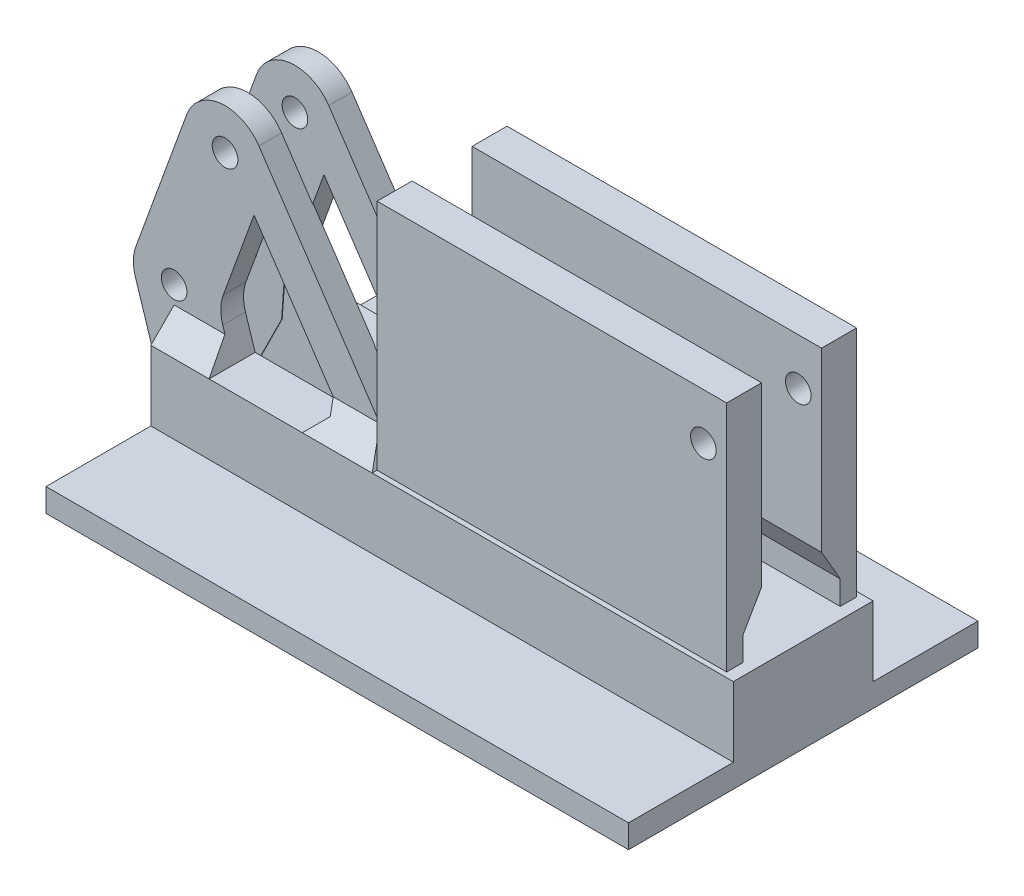
SolidWorks part; units mm, degrees
material "ABS"
ref_plane "前视基准面" through (0, 0, 0) normal (0, 0, 1) x (1, 0, 0)
ref_plane "上视基准面" through (0, 0, 0) normal (0, 1, 0) x (1, 0, 0)
ref_plane "右视基准面" through (0, 0, 0) normal (1, 0, 0) x (0, 0, -1)
other "Configuration Table"
sketch "草图1" plane through (0, 0, 0) normal (0, 1, 0) x (1, 0, 0)
  line L1 (-25, 15) -> (25, 15)
  line L2 (-25, 15) -> (-25, -15)
  line L3 (-25, -15) -> (25, -15)
  line L4 (25, 15) -> (25, -15)
  line L5 (-25, 15) -> (25, -15) construction
  line L6 (-25, -15) -> (25, 15) construction
  point P0 (0, 0)
  dimension "D1" = 30
  dimension "D2" = 50
extrude "凸台-拉伸1" add sketch "草图1" along normal mid plane 8
sketch "草图2" plane through (0, 0, 0) normal (0, 0, 1) x (1, 0, 0)
  line L0 (-25, 7.5) -> (-20.6324, 19.5) construction
  line L1 (-25, 4) -> (25, 4) construction
  line L2 (-25, 4) -> (-25, -4) construction
  line L3 (-25, -4) -> (-28.334, 6.4348)
  line L4 (-28.2889, 8.6971) -> (-23.9213, 20.6971)
  line L5 (-17.3434, 18.3029) -> (-20.7828, 8.8533)
  line L6 (-20.8278, 6.591) -> (-20, 4)
  line L7 (-25, -4) -> (-20, 4)
  circle A0 centre (-25, 7.5) radius 1.1
  circle A1 centre (-20.6324, 19.5) radius 1.1
  arc A2 (-28.334, 6.4348) -> (-28.2889, 8.6971) centre (-25, 7.5) cw
  arc A3 (-23.9213, 20.6971) -> (-17.3434, 18.3029) centre (-20.6324, 19.5) cw
  arc A4 (-20.7828, 8.8533) -> (-20.8278, 6.591) centre (-17.4939, 7.6563) ccw
  dimension "D4" = 2.2
  dimension "D5" = 3.5
  dimension "D1" = 15.5
  dimension "D2" = 70
  dimension "D3" = 3.5
  dimension "D6" = 5
extrude "凸台-拉伸2" add sketch "草图2" along normal mid plane 8
sketch "草图3" plane through (0, 0, 0) normal (0, 0, 1) x (1, 0, 0)
  line L0 (-28.1087, 9.1922) -> (-25.3291, 16.8291)
  line L2 (-23.9213, 20.6971) -> (-28.2889, 8.6971) construction
  line L3 (-20.7828, 8.8533) -> (-18.7512, 14.435)
  line L5 (-20.7828, 8.8533) -> (-17.3434, 18.3029) construction
  line L6 (-25, 7.5) -> (-20.6324, 19.5) construction
  line L7 (-28.2889, 8.6971) -> (-23.9213, 20.6971)
  line L8 (-21.7111, 6.3029) -> (-17.3434, 18.3029)
  line L9 (-25, -4) -> (-28.334, 6.4348)
  line L10 (-25, -4) -> (-21.7111, 6.3029)
  line L11 (-28.334, 6.4348) -> (-25, -4) construction
  line L12 (-21.7111, 6.3029) -> (-20.5376, 5.9283)
  line L13 (-20.5376, 5.9283) -> (-20.7828, 8.8533)
  arc A3 (-28.2889, 8.6971) -> (-21.7111, 6.3029) centre (-25, 7.5) ccw
  arc A4 (-17.3434, 18.3029) -> (-23.9213, 20.6971) centre (-20.6324, 19.5) ccw
  arc A5 (-20.7828, 8.8533) -> (-20.8278, 6.591) centre (-17.4939, 7.6563) ccw construction
  point P3 (-22.8162, 13.5)
extrude "切除-拉伸1" cut sketch "草图3" against normal mid plane 4 contours L8 A4 L7 L0 A3 L3 | A3 L9 L10 | L12 L13 L8 region at (-22.8162, 13.5, 0) region at (-25.0015, 1.6723, 0) region at (-21.0105, 7.0282, 0)
sketch "草图4" plane through (0, 0, 4) normal (0, 0, 1) x (1, 0, 0)
  line L0 (-17.7273, 21.4521) -> (-6, 4)
  line L1 (-25, 4) -> (25, 4) construction
  line L2 (-6, 4) -> (-10, 4)
  line L3 (-10, 4) -> (-18.1402, 16.1139)
  line L4 (-20.7828, 8.8533) -> (-17.3434, 18.3029) construction
  line L5 (-18.1402, 16.1139) -> (-17.7273, 21.4521)
  circle A0 centre (-25, 7.5) radius 1.1 construction
  arc A1 (-17.3434, 18.3029) -> (-23.9213, 20.6971) centre (-20.6324, 19.5) ccw construction
  dimension "4" = 4
  dimension "D2" = 10
extrude "凸台-拉伸3" add sketch "草图4" against normal blind 2
mirror "镜向1" about plane through (0, 0, 0) normal (0, 0, 1) of "凸台-拉伸3"
sketch "草图6" plane through (0, 0, 0) normal (0, 0, 1) x (1, 0, 0)
  line L0 (-20.6324, 19.5) -> (-22.274, -3.4413) construction
  line L1 (-25, 4) -> (25, 4) construction
  line L2 (-20.6324, 19.5) -> (-3.6397, 4) construction
  line L3 (-21.5089, 7.2502) -> (-22.274, -3.4413)
  line L4 (-3.6397, 4) -> (-11.5589, 11.2236)
  line L5 (-25.0576, -3.0703) -> (-21.7744, 3.5408)
  line L6 (-25.0576, -3.0703) -> (-20.6324, 19.5) construction
  arc A0 (-21.5089, 7.2502) -> (-11.5589, 11.2236) centre (-20.6324, 19.5) ccw
  arc A1 (-22.274, -3.4413) -> (-3.6397, 4) centre (-20.6324, 19.5) ccw
  circle A3 centre (-25, 7.5) radius 3.5 construction
  arc A4 (-22.274, -3.4413) -> (-25.0576, -3.0703) centre (-20.6324, 19.5) cw
  dimension "D1" = 7
  dimension "D2" = 23
  dimension "D3" = 7
  dimension "D4" = 7
extrude "切除-拉伸3" cut sketch "草图6" against normal mid plane 4.1 contours L3 A1 L4 A0 | A4 L3 L5 region at (-14.1156, 3.1809, 0) region at (-23.0405, -1.0088, 0)
sketch "草图7" plane through (0, 4, 0) normal (0, 1, 0) x (1, 0, 0)
  line L0 (0, 0) -> (50000, 0) construction
  line L1 (-6, -2.575) -> (24, -2.575)
  line L2 (-6, 5.575) -> (24, 5.575)
  line L3 (-6, 5.575) -> (-6, 2.575)
  line L4 (-6, 2.575) -> (24, 2.575)
  line L5 (24, 5.575) -> (24, 2.575)
  line L6 (24, -5.575) -> (24, -2.575)
  line L7 (-6, -5.575) -> (24, -5.575)
  line L8 (-6, -5.575) -> (-6, -2.575)
  line L9 (-6, 2.05) -> (-6, 4) construction
  dimension "D1" = 30
  dimension "D2" = 3
  dimension "D3" = 5.15
extrude "凸台-拉伸4" add sketch "草图7" along normal blind 20
fillet "圆角3" radius 2 1 edges at (-21.5797, 6.261, 0)
chamfer "倒角2" distance 2 angle 45 6 edges at (-8, 4, -4) (-10, 4, -3.025) (-8, 4, 4) (-10, 4, 3.025) (-22.5, 4, -4) (-22.5, 4, 4) first distance on face at (-20.3858, 8.5622, -4) first distance on face at (-13.9247, 9.8406, -2.6833) first distance on face at (-4.6171, 4, 0)
sketch "草图8" plane through (0, 0, 0) normal (0, 0, 1) x (1, 0, 0)
  line L0 (-3, 6) -> (12, 6) construction
  line L1 (-3, 7.2) -> (12, 7.2)
  line L2 (-3, 4.8) -> (12, 4.8)
  line L3 (-25, 4) -> (25, 4) construction
  line L4 (-6, 24) -> (-6, 4) construction
  arc A0 (-3, 7.2) -> (-3, 4.8) centre (-3, 6) ccw
  arc A1 (12, 4.8) -> (12, 7.2) centre (12, 6) ccw
  point P2 (4.5, 6)
  dimension "D1" = 1.2
  dimension "D2" = 15
  dimension "D3" = 2
  dimension "D4" = 3
extrude "切除-拉伸4" [suppressed] cut sketch "草图8" against normal through all and the other way through all
sketch "草图9" plane through (0, 4, 0) normal (0, 1, 0) x (1, 0, 0)
  line L0 (0, 0) -> (-50000, 0) construction
  line L1 (25, -15) -> (25, 15) construction
  line L2 (-25, 15) -> (25, 15)
  line L3 (-25, 15) -> (-25, 6)
  line L4 (-25, 6) -> (25, 6)
  line L5 (25, 15) -> (25, 6)
  line L6 (-25, -6) -> (25, -6)
  line L7 (25, -15) -> (25, -6)
  line L8 (-25, -15) -> (25, -15)
  line L9 (-25, -15) -> (-25, -6)
  line L10 (-3.6397, -2.05) -> (-25.0576, -2.05) construction
  line L11 (-25.0576, 2) -> (-15.0576, 2)
  line L12 (-25.0576, 2) -> (-25.0576, -2.05)
  line L13 (-25.0576, -2.05) -> (-15.0576, -2.05)
  line L14 (-15.0576, 2) -> (-15.0576, -2.05)
  line M6 (-25, 15) -> (-25, 6)
  line M7 (-25, 6) -> (-20, 6)
  line M11 (-11.4412, 6) -> (-6, 6)
  line M21 (-6, -6) -> (-12, -6)
  line M23 (-12, -2.05) -> (-20, -2.05)
  line M25 (-20, -6) -> (-25, -6)
  line M26 (-25, -6) -> (-25, -15)
  line M27 (-25, -15) -> (25, -15)
  line M28 (25, -15) -> (25, 15)
  line M29 (25, 15) -> (-25, 15)
  dimension "D1" = 9
  dimension "D2" = 10
extrude "切除-拉伸5" cut sketch "草图9" against normal offset from surface 2 and the other way through all contours L14 L0 L12 L13 M23 | L0 L14 L11 L12 | L4 M7 M11 M28 M29 M6 | L6 M25 M26 M27 M28 M21 region at (-20.0576, 4, 1.025) region at (-20.0576, 4, -1) region at (0, 4, 10.5) region at (0, 4, -10.5) up to face at (-12.5, -4, 0)
sketch "草图10" plane through (24, 0, 0) normal (1, 0, 0) x (0, 0, -1)
  line L0 (0, 0.0713) -> (0, -49999.9287) construction
  line L9 (-2.575, 4) -> (-4.175, 4)
  line L10 (-5.575, 4) -> (-2.575, 4) construction
  line L11 (-4.175, 4) -> (-4.175, 6.05)
  line L12 (-4.175, 6.05) -> (-2.575, 8.8213)
  line L13 (-2.575, 24) -> (-2.575, 4) construction
  line L14 (-2.575, 8.8213) -> (-2.575, 4)
  line L15 (4.175, 6.05) -> (2.575, 8.8213)
  line L16 (4.175, 4) -> (4.175, 6.05)
  line L17 (2.575, 4) -> (4.175, 4)
  line L18 (2.575, 8.8213) -> (2.575, 4)
  dimension "D1" = 1.6
  dimension "D2" = 30
  dimension "D3" = 2.05
extrude "切除-拉伸6" cut sketch "草图10" against normal up to surface (30 mm away) up to face at (-6, 14, 4.075)
sketch "草图11" plane through (0, 0, 0) normal (0, 0, 1) x (1, 0, 0)
  line L0 (-25, 6) -> (-25, -4) construction
  line L1 (-6, 4) -> (24, 4) construction
  circle A0 centre (22, 20) radius 1.1
  dimension "D1" = 2.2
  dimension "D2" = 47
  dimension "D3" = 16
extrude "切除-拉伸7" cut sketch "草图11" against normal through all and the other way through all
